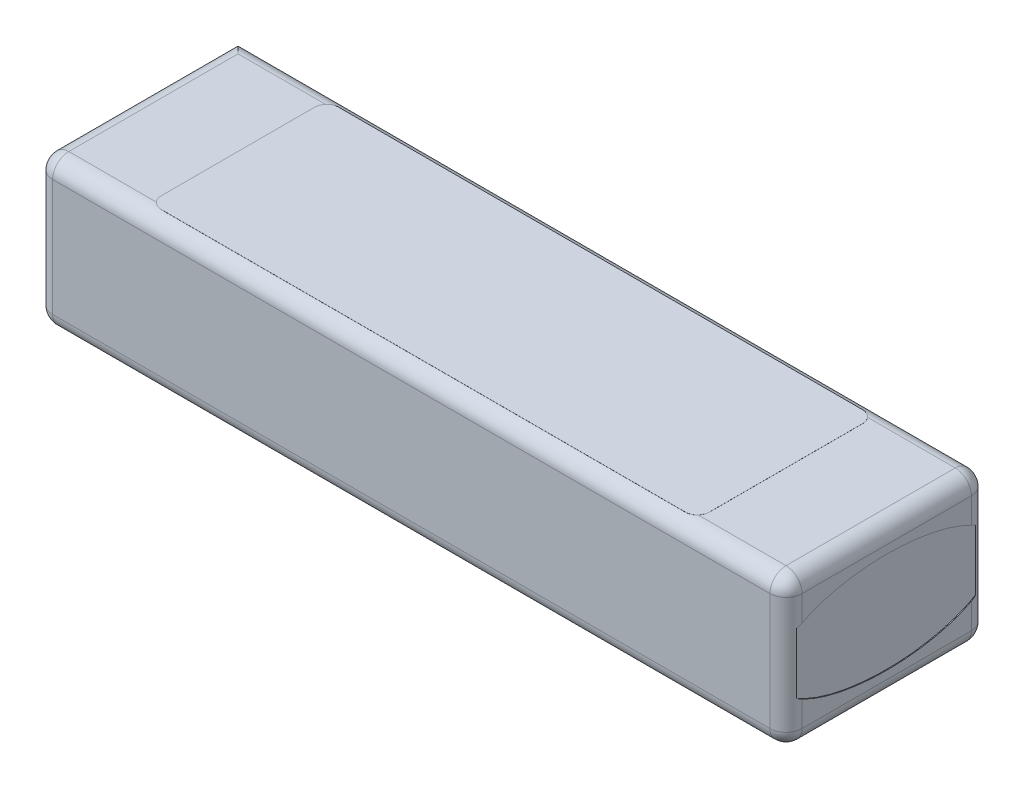
SolidWorks part; units mm, degrees
ref_plane "Front Plane" through (0, 0, 0) normal (0, 0, 1) x (1, 0, 0)
ref_plane "Top Plane" through (0, 0, 0) normal (0, 1, 0) x (1, 0, 0)
ref_plane "Right Plane" through (0, 0, 0) normal (1, 0, 0) x (0, 0, -1)
sketch "Sketch1" plane through (0, 0, 0) normal (0, 1, 0) x (1, 0, 0)
  line L1 (-46.5, 12.5) -> (46.5, 12.5)
  line L2 (-46.5, 12.5) -> (-46.5, -12.5)
  line L3 (-46.5, -12.5) -> (46.5, -12.5)
  line L4 (46.5, 12.5) -> (46.5, -12.5)
  line L5 (-46.5, 12.5) -> (46.5, -12.5) construction
  line L6 (-46.5, -12.5) -> (46.5, 12.5) construction
  point P0 (0, 0)
  dimension "D1" = 93
  dimension "D2" = 25
extrude "Boss-Extrude1" add sketch "Sketch1" along normal blind 18.5
fillet "Fillet1" radius 2 4 edges at (-46.5, 18.5, 0) (-46.5, 0, 0) (46.5, 0, 0) (46.5, 18.5, 0)
fillet "Fillet2" radius 2 11 edges at (45.9142, 17.9142, 12.5) (46.5, 9.25, 12.5) (45.9142, 0.5858, 12.5) (0, 0, 12.5) (-45.9142, 0.5858, 12.5) (-46.5, 9.25, 12.5) (-45.9142, 17.9142, 12.5) (0, 18.5, 12.5) (0, 0, -12.5) (46.5, 9.25, -12.5) (0, 18.5, -12.5)
sketch "Sketch3" plane through (0, 18.5, 0) normal (0, 1, 0) x (-1, 0, 0)
  line L1 (-32.5, 11) -> (32.5, 11)
  line L2 (-34, 9.5) -> (-34, -9.5)
  line L3 (-32.5, -11) -> (32.5, -11)
  line L4 (34, 9.5) -> (34, -9.5)
  line L5 (-34, 11) -> (34, -11) construction
  line L6 (-34, -11) -> (34, 11) construction
  arc A0 (34, 9.5) -> (32.5, 11) centre (32.5, 9.5) ccw
  arc A1 (-32.5, 11) -> (-34, 9.5) centre (-32.5, 9.5) ccw
  arc A2 (-34, -9.5) -> (-32.5, -11) centre (-32.5, -9.5) ccw
  arc A3 (32.5, -11) -> (34, -9.5) centre (32.5, -9.5) ccw
  point P0 (0, 0)
  dimension "D3" = 1.5
  dimension "D1" = 68
  dimension "D2" = 22
extrude "Boss-Extrude2" add sketch "Sketch3" along normal blind 0.01
sketch "Sketch4" plane through (46.5, 0, 0) normal (1, 0, 0) x (0, 0, -1)
  ellipse E0 centre (0, 9.25) end of major axis (-13.8959, 9.25) minor radius 6.2461
extrude "Cut-Extrude1" cut sketch "Sketch4" against normal blind 0.1
sketch "Sketch5" plane through (-46.5, 0, 0) normal (-1, 0, 0) x (0, 0, 1)
  ellipse E0 centre (-7.2077, 9.25) end of major axis (-28.912, 9.25) minor radius 7.0582
extrude "Cut-Extrude2" cut sketch "Sketch5" against normal blind 0.1
sketch "Sketch7" plane through (-46.4, 0, 0) normal (-1, 0, 0) x (0, 0, 1)
  line L0 (10.5, 16.5) -> (-12.5, 16.5) construction
  line L1 (-12.5, 2) -> (10.5, 2) construction
  line L2 (-12.5, 16.0952) -> (-12.5, 2.4048) construction
  circle A0 centre (-10.7, 14.5) radius 1.75
  circle A5 centre (-10.7, 4) radius 1.75
  dimension "D1" = 2
  dimension "D2" = 2
  dimension "D4" = 1.8
sketch3d "3DSketch4"
  line L0 (3.2157, 4.3574, 15.741) -> (2.2157, 4.1966, 15.9554) construction
  point P0 (-48.1897, 4.1091, -11.0514)
  point P1 (-51.7038, 4.1091, -7.5115)
  point P3 (-49.2763, 4.4209, 14.5124)
  point P5 (2.7157, 4.277, 15.8482)
sweep "Sweep4" [suppressed] add profiles "Sketch7" path "3DSketch4"
sketch "Sketch10" plane through (-46.4, 0, 0) normal (-1, 0, 0) x (0, 0, 1)
  line L0 (10.5, 16.5) -> (-12.5, 16.5) construction
  circle A0 centre (-16.0811, 12.025) radius 0.9
  circle A1 centre (-16.0811, 10.175) radius 0.9
  circle A2 centre (-16.0811, 8.325) radius 0.9
  circle A3 centre (-16.0811, 6.475) radius 0.9
  dimension "D2" = 4.475
  dimension "D1" = 4
sketch3d "3DSketch5"
  spline S0 degree 3 poles (-49.9, 7.2687, -16.0469) (-53.2389, 7.2687, -16.6261) (-51.145, 7.2687, -20.0709) (-44.8149, 7.2687, -20.6833) (-33.289, 7.2687, -18.1691) (-23.6599, 7.2687, -20.104) (-13.5898, 7.2687, -19.7953) knots 0 0 0 0 0.156251 0.191544 0.414675 1 1 1 1
sweep "Sweep5" [suppressed] add profiles "Sketch10" path "3DSketch5"
sketch "Sketch11" plane through (-46.4, 0, 0) normal (-1, 0, 0) x (0, 0, 1)
  line L1 (-12, 16.0952) -> (-15.4847, 16.0952)
  line L2 (-12.5, 15.5952) -> (-12.5, 3.451)
  line L3 (-12, 2.951) -> (-15.4847, 2.951)
  line L4 (-14.9847, 15.5952) -> (-14.9847, 3.451)
  arc A0 (-12.5, 3.451) -> (-12, 2.951) centre (-12, 3.451) ccw
  arc A1 (-15.4847, 2.951) -> (-14.9847, 3.451) centre (-15.4847, 3.451) ccw
  arc A2 (-14.9847, 15.5952) -> (-15.4847, 16.0952) centre (-15.4847, 15.5952) ccw
  arc A3 (-12, 16.0952) -> (-12.5, 15.5952) centre (-12, 15.5952) ccw
  point P13 (-12.5, 16.0952)
  dimension "D1" = 0.5
extrude "Boss-Extrude3" [suppressed] add sketch "Sketch11" along normal blind 0.05
